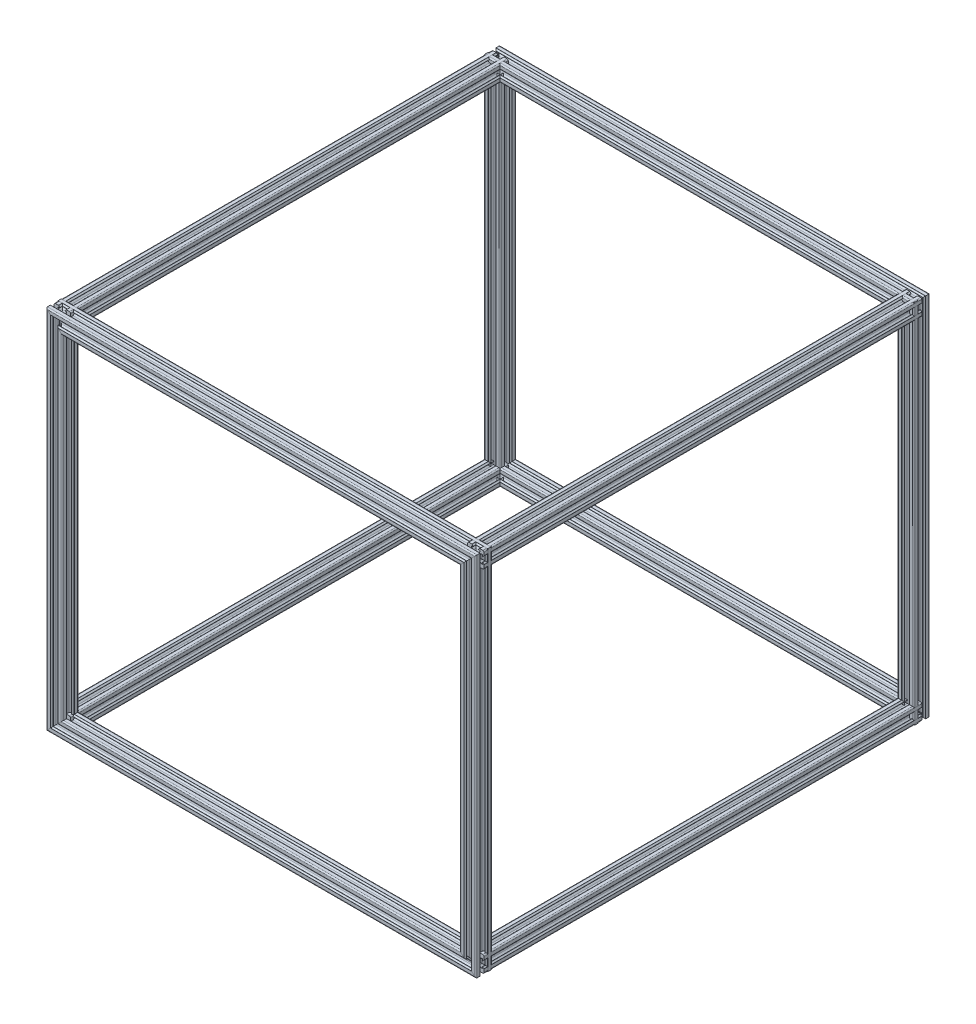
SolidWorks part; units mm, degrees
material "6061 Alloy"
ref_plane "Front Plane" through (0, 0, 0) normal (0, 0, 1) x (1, 0, 0)
ref_plane "Top Plane" through (0, 0, 0) normal (0, 1, 0) x (1, 0, 0)
ref_plane "Right Plane" through (0, 0, 0) normal (1, 0, 0) x (0, 0, -1)
sketch "Sketch1" plane through (0, 0, 0) normal (0, 0, 1) x (1, 0, 0)
  line L1 (-255, 215.9) -> (255, 215.9)
  line L2 (-255, 215.9) -> (-255, -215.9)
  line L3 (-255, -215.9) -> (255, -215.9)
  line L4 (255, 215.9) -> (255, -215.9)
  line L5 (-255, 215.9) -> (255, -215.9) construction
  line L6 (-255, -215.9) -> (255, 215.9) construction
  point P0 (0, 0)
  dimension "D1" = 510
  dimension "D2" = 431.8
ref_plane "Plane1" through (0, 0, 540) normal (0, 0, 1) x (1, 0, 0)
sketch3d "3DSketch2"
  line L0 (255, 215.9, 0) -> (255, -215.9, 0) construction
  line L1 (255, 215.9, 0) -> (255, -215.9, 0)
  line L2 (-255, 215.9, 0) -> (-255, -215.9, 0) construction
  line L3 (-255, 215.9, 0) -> (-255, -215.9, 0)
  line L8 (255, 215.9, 0) -> (-255, 215.9, 0)
  line L9 (255, -215.9, 0) -> (255, 215.9, 0)
  line L10 (-255, -215.9, 0) -> (255, -215.9, 0)
  line L11 (-255, 215.9, 0) -> (-255, -215.9, 0)
  line L12 (255, 215.9, 0) -> (-255, 215.9, 0)
  line L13 (255, -215.9, 0) -> (255, 215.9, 0)
  line L14 (-255, -215.9, 0) -> (255, -215.9, 0)
  line L15 (-255, 215.9, 0) -> (-255, -215.9, 0)
  dimension "D1" = 0
sketch "Sketch2" plane through (0, 0, 540) normal (0, 0, 1) x (1, 0, 0)
  line L4 (255, 215.9) -> (-255, 215.9)
  line L5 (255, -215.9) -> (255, 215.9)
  line L6 (-255, -215.9) -> (255, -215.9)
  line L7 (-255, 215.9) -> (-255, -215.9)
  line L8 (255, 215.9) -> (-255, 215.9)
  line L9 (255, -215.9) -> (255, 215.9)
  line L10 (-255, -215.9) -> (255, -215.9)
  line L11 (-255, 215.9) -> (-255, -215.9)
  dimension "D1" = 0
sketch3d "3DSketch3"
  line L0 (255, 215.9, 0) -> (255, 215.9, 540)
  line L1 (-255, 215.9, 0) -> (-255, 215.9, 540)
  line L2 (-255, -215.9, 0) -> (-255, -215.9, 540)
  line L3 (255, -215.9, 0) -> (255, -215.9, 540)
other "Profile_20х20 20X20(1)" corner treatment miter
ref_plane "Plane2" through (-255, 215.9, 540) normal (0, -1, 0) x (1, 0, 0)
sketch "Сечение" plane through (-255, 215.9, 540) normal (0, -1, 0) x (1, 0, 0)
  line L0 (-4, 1.8988) -> (-4, 0.3377)
  line L1 (-3.9452, 0.1815) -> (-3.8, 0)
  line L2 (-3.8, 0) -> (-3.9452, -0.1815)
  line L3 (-4, -0.3377) -> (-4, -1.8988)
  line L4 (-4.5858, -3.313) -> (-6.2799, -5.0071)
  line L5 (-6.987, -5.3) -> (-7.8, -5.3)
  line L6 (-8, -5.1) -> (-8, -3.33)
  line L7 (-8.4268, -3.1532) -> (-9.9268, -4.6532)
  line L8 (-10, -4.83) -> (-10, -8.5)
  line L9 (-8.5, -10) -> (-4.83, -10)
  line L10 (-4.6532, -9.9268) -> (-3.1532, -8.4268)
  line L11 (-3.33, -8) -> (-5.1, -8)
  line L12 (-5.3, -7.8) -> (-5.3, -6.987)
  line L13 (-5.0071, -6.2799) -> (-3.313, -4.5858)
  line L14 (-1.8988, -4) -> (-0.3377, -4)
  line L15 (-0.1815, -3.9452) -> (0, -3.8)
  line L16 (0, -3.8) -> (0.1815, -3.9452)
  line L17 (0.3377, -4) -> (1.8988, -4)
  line L18 (3.313, -4.5858) -> (5.0071, -6.2799)
  line L19 (5.3, -6.987) -> (5.3, -7.8)
  line L20 (5.1, -8) -> (3.33, -8)
  line L21 (3.1532, -8.4268) -> (4.6532, -9.9268)
  line L22 (4.83, -10) -> (8.5, -10)
  line L23 (10, -8.5) -> (10, -4.83)
  line L24 (9.9268, -4.6532) -> (8.4268, -3.1532)
  line L25 (8, -3.33) -> (8, -5.1)
  line L26 (7.8, -5.3) -> (6.987, -5.3)
  line L27 (6.2799, -5.0071) -> (4.5858, -3.313)
  line L28 (4, -1.8988) -> (4, -0.3377)
  line L29 (3.9452, -0.1815) -> (3.8, 0)
  line L30 (3.8, 0) -> (3.9452, 0.1815)
  line L31 (4, 0.3377) -> (4, 1.8988)
  line L32 (4.5858, 3.313) -> (6.2799, 5.0071)
  line L33 (6.987, 5.3) -> (7.8, 5.3)
  line L34 (8, 5.1) -> (8, 3.33)
  line L35 (8.4268, 3.1532) -> (9.9268, 4.6532)
  line L36 (10, 4.83) -> (10, 8.5)
  line L37 (8.5, 10) -> (4.83, 10)
  line L38 (4.6532, 9.9268) -> (3.1532, 8.4268)
  line L39 (3.33, 8) -> (5.1, 8)
  line L40 (5.3, 7.8) -> (5.3, 6.987)
  line L41 (5.0071, 6.2799) -> (3.313, 4.5858)
  line L42 (1.8988, 4) -> (0.3377, 4)
  line L43 (0.1815, 3.9452) -> (0, 3.8)
  line L44 (0, 3.8) -> (-0.1815, 3.9452)
  line L45 (-0.3377, 4) -> (-1.8988, 4)
  line L46 (-3.313, 4.5858) -> (-5.0071, 6.2799)
  line L47 (-5.3, 6.987) -> (-5.3, 7.8)
  line L48 (-5.1, 8) -> (-3.33, 8)
  line L49 (-3.1532, 8.4268) -> (-4.6532, 9.9268)
  line L50 (-4.83, 10) -> (-8.5, 10)
  line L51 (-10, 8.5) -> (-10, 4.83)
  line L52 (-9.9268, 4.6532) -> (-8.4268, 3.1532)
  line L53 (-8, 3.33) -> (-8, 5.1)
  line L54 (-7.8, 5.3) -> (-6.987, 5.3)
  line L55 (-6.2799, 5.0071) -> (-4.5858, 3.313)
  circle A0 centre (0, 0) radius 2.5
  arc A1 (-4, 0.3377) -> (-3.9452, 0.1815) centre (-3.75, 0.3377) ccw
  arc A2 (-3.9452, -0.1815) -> (-4, -0.3377) centre (-3.75, -0.3377) ccw
  arc A3 (-4, -1.8988) -> (-4.5858, -3.313) centre (-6, -1.8988) cw
  arc A4 (-6.2799, -5.0071) -> (-6.987, -5.3) centre (-6.987, -4.3) cw
  arc A5 (-7.8, -5.3) -> (-8, -5.1) centre (-7.8, -5.1) cw
  arc A6 (-8, -3.33) -> (-8.4268, -3.1532) centre (-8.25, -3.33) ccw
  arc A7 (-9.9268, -4.6532) -> (-10, -4.83) centre (-9.75, -4.83) ccw
  arc A8 (-10, -8.5) -> (-8.5, -10) centre (-8.5, -8.5) ccw
  arc A9 (-4.83, -10) -> (-4.6532, -9.9268) centre (-4.83, -9.75) ccw
  arc A10 (-3.1532, -8.4268) -> (-3.33, -8) centre (-3.33, -8.25) ccw
  arc A11 (-5.1, -8) -> (-5.3, -7.8) centre (-5.1, -7.8) cw
  arc A12 (-5.3, -6.987) -> (-5.0071, -6.2799) centre (-4.3, -6.987) cw
  arc A13 (-3.313, -4.5858) -> (-1.8988, -4) centre (-1.8988, -6) cw
  arc A14 (-0.3377, -4) -> (-0.1815, -3.9452) centre (-0.3377, -3.75) ccw
  arc A15 (0.1815, -3.9452) -> (0.3377, -4) centre (0.3377, -3.75) ccw
  arc A16 (1.8988, -4) -> (3.313, -4.5858) centre (1.8988, -6) cw
  arc A17 (5.0071, -6.2799) -> (5.3, -6.987) centre (4.3, -6.987) cw
  arc A18 (5.3, -7.8) -> (5.1, -8) centre (5.1, -7.8) cw
  arc A19 (3.33, -8) -> (3.1532, -8.4268) centre (3.33, -8.25) ccw
  arc A20 (4.6532, -9.9268) -> (4.83, -10) centre (4.83, -9.75) ccw
  arc A21 (8.5, -10) -> (10, -8.5) centre (8.5, -8.5) ccw
  arc A22 (10, -4.83) -> (9.9268, -4.6532) centre (9.75, -4.83) ccw
  arc A23 (8.4268, -3.1532) -> (8, -3.33) centre (8.25, -3.33) ccw
  arc A24 (8, -5.1) -> (7.8, -5.3) centre (7.8, -5.1) cw
  arc A25 (6.987, -5.3) -> (6.2799, -5.0071) centre (6.987, -4.3) cw
  arc A26 (4.5858, -3.313) -> (4, -1.8988) centre (6, -1.8988) cw
  arc A27 (4, -0.3377) -> (3.9452, -0.1815) centre (3.75, -0.3377) ccw
  arc A28 (3.9452, 0.1815) -> (4, 0.3377) centre (3.75, 0.3377) ccw
  arc A29 (4, 1.8988) -> (4.5858, 3.313) centre (6, 1.8988) cw
  arc A30 (6.2799, 5.0071) -> (6.987, 5.3) centre (6.987, 4.3) cw
  arc A31 (7.8, 5.3) -> (8, 5.1) centre (7.8, 5.1) cw
  arc A32 (8, 3.33) -> (8.4268, 3.1532) centre (8.25, 3.33) ccw
  arc A33 (9.9268, 4.6532) -> (10, 4.83) centre (9.75, 4.83) ccw
  arc A34 (10, 8.5) -> (8.5, 10) centre (8.5, 8.5) ccw
  arc A35 (4.83, 10) -> (4.6532, 9.9268) centre (4.83, 9.75) ccw
  arc A36 (3.1532, 8.4268) -> (3.33, 8) centre (3.33, 8.25) ccw
  arc A37 (5.1, 8) -> (5.3, 7.8) centre (5.1, 7.8) cw
  arc A38 (5.3, 6.987) -> (5.0071, 6.2799) centre (4.3, 6.987) cw
  arc A39 (3.313, 4.5858) -> (1.8988, 4) centre (1.8988, 6) cw
  arc A40 (0.3377, 4) -> (0.1815, 3.9452) centre (0.3377, 3.75) ccw
  arc A41 (-0.1815, 3.9452) -> (-0.3377, 4) centre (-0.3377, 3.75) ccw
  arc A42 (-1.8988, 4) -> (-3.313, 4.5858) centre (-1.8988, 6) cw
  arc A43 (-5.0071, 6.2799) -> (-5.3, 6.987) centre (-4.3, 6.987) cw
  arc A44 (-5.3, 7.8) -> (-5.1, 8) centre (-5.1, 7.8) cw
  arc A45 (-3.33, 8) -> (-3.1532, 8.4268) centre (-3.33, 8.25) ccw
  arc A46 (-4.6532, 9.9268) -> (-4.83, 10) centre (-4.83, 9.75) ccw
  arc A47 (-8.5, 10) -> (-10, 8.5) centre (-8.5, 8.5) ccw
  arc A48 (-10, 4.83) -> (-9.9268, 4.6532) centre (-9.75, 4.83) ccw
  arc A49 (-8.4268, 3.1532) -> (-8, 3.33) centre (-8.25, 3.33) ccw
  arc A50 (-8, 5.1) -> (-7.8, 5.3) centre (-7.8, 5.1) cw
  arc A51 (-6.987, 5.3) -> (-6.2799, 5.0071) centre (-6.987, 4.3) cw
  arc A52 (-4.5858, 3.313) -> (-4, 1.8988) centre (-6, 1.8988) cw
  point P162 (0, 0)
other "Profile_20х20 20X20(2)" corner treatment miter
ref_plane "Plane3" through (-255, 215.9, 0) normal (0, 0, 1) x (1, 0, 0)
sketch "Сечение1" plane through (-255, 215.9, 0) normal (0, 0, 1) x (1, 0, 0)
  line L0 (-4, 1.8988) -> (-4, 0.3377)
  line L1 (-3.9452, 0.1815) -> (-3.8, 0)
  line L2 (-3.8, 0) -> (-3.9452, -0.1815)
  line L3 (-4, -0.3377) -> (-4, -1.8988)
  line L4 (-4.5858, -3.313) -> (-6.2799, -5.0071)
  line L5 (-6.987, -5.3) -> (-7.8, -5.3)
  line L6 (-8, -5.1) -> (-8, -3.33)
  line L7 (-8.4268, -3.1532) -> (-9.9268, -4.6532)
  line L8 (-10, -4.83) -> (-10, -8.5)
  line L9 (-8.5, -10) -> (-4.83, -10)
  line L10 (-4.6532, -9.9268) -> (-3.1532, -8.4268)
  line L11 (-3.33, -8) -> (-5.1, -8)
  line L12 (-5.3, -7.8) -> (-5.3, -6.987)
  line L13 (-5.0071, -6.2799) -> (-3.313, -4.5858)
  line L14 (-1.8988, -4) -> (-0.3377, -4)
  line L15 (-0.1815, -3.9452) -> (0, -3.8)
  line L16 (0, -3.8) -> (0.1815, -3.9452)
  line L17 (0.3377, -4) -> (1.8988, -4)
  line L18 (3.313, -4.5858) -> (5.0071, -6.2799)
  line L19 (5.3, -6.987) -> (5.3, -7.8)
  line L20 (5.1, -8) -> (3.33, -8)
  line L21 (3.1532, -8.4268) -> (4.6532, -9.9268)
  line L22 (4.83, -10) -> (8.5, -10)
  line L23 (10, -8.5) -> (10, -4.83)
  line L24 (9.9268, -4.6532) -> (8.4268, -3.1532)
  line L25 (8, -3.33) -> (8, -5.1)
  line L26 (7.8, -5.3) -> (6.987, -5.3)
  line L27 (6.2799, -5.0071) -> (4.5858, -3.313)
  line L28 (4, -1.8988) -> (4, -0.3377)
  line L29 (3.9452, -0.1815) -> (3.8, 0)
  line L30 (3.8, 0) -> (3.9452, 0.1815)
  line L31 (4, 0.3377) -> (4, 1.8988)
  line L32 (4.5858, 3.313) -> (6.2799, 5.0071)
  line L33 (6.987, 5.3) -> (7.8, 5.3)
  line L34 (8, 5.1) -> (8, 3.33)
  line L35 (8.4268, 3.1532) -> (9.9268, 4.6532)
  line L36 (10, 4.83) -> (10, 8.5)
  line L37 (8.5, 10) -> (4.83, 10)
  line L38 (4.6532, 9.9268) -> (3.1532, 8.4268)
  line L39 (3.33, 8) -> (5.1, 8)
  line L40 (5.3, 7.8) -> (5.3, 6.987)
  line L41 (5.0071, 6.2799) -> (3.313, 4.5858)
  line L42 (1.8988, 4) -> (0.3377, 4)
  line L43 (0.1815, 3.9452) -> (0, 3.8)
  line L44 (0, 3.8) -> (-0.1815, 3.9452)
  line L45 (-0.3377, 4) -> (-1.8988, 4)
  line L46 (-3.313, 4.5858) -> (-5.0071, 6.2799)
  line L47 (-5.3, 6.987) -> (-5.3, 7.8)
  line L48 (-5.1, 8) -> (-3.33, 8)
  line L49 (-3.1532, 8.4268) -> (-4.6532, 9.9268)
  line L50 (-4.83, 10) -> (-8.5, 10)
  line L51 (-10, 8.5) -> (-10, 4.83)
  line L52 (-9.9268, 4.6532) -> (-8.4268, 3.1532)
  line L53 (-8, 3.33) -> (-8, 5.1)
  line L54 (-7.8, 5.3) -> (-6.987, 5.3)
  line L55 (-6.2799, 5.0071) -> (-4.5858, 3.313)
  circle A0 centre (0, 0) radius 2.5
  arc A1 (-4, 0.3377) -> (-3.9452, 0.1815) centre (-3.75, 0.3377) ccw
  arc A2 (-3.9452, -0.1815) -> (-4, -0.3377) centre (-3.75, -0.3377) ccw
  arc A3 (-4, -1.8988) -> (-4.5858, -3.313) centre (-6, -1.8988) cw
  arc A4 (-6.2799, -5.0071) -> (-6.987, -5.3) centre (-6.987, -4.3) cw
  arc A5 (-7.8, -5.3) -> (-8, -5.1) centre (-7.8, -5.1) cw
  arc A6 (-8, -3.33) -> (-8.4268, -3.1532) centre (-8.25, -3.33) ccw
  arc A7 (-9.9268, -4.6532) -> (-10, -4.83) centre (-9.75, -4.83) ccw
  arc A8 (-10, -8.5) -> (-8.5, -10) centre (-8.5, -8.5) ccw
  arc A9 (-4.83, -10) -> (-4.6532, -9.9268) centre (-4.83, -9.75) ccw
  arc A10 (-3.1532, -8.4268) -> (-3.33, -8) centre (-3.33, -8.25) ccw
  arc A11 (-5.1, -8) -> (-5.3, -7.8) centre (-5.1, -7.8) cw
  arc A12 (-5.3, -6.987) -> (-5.0071, -6.2799) centre (-4.3, -6.987) cw
  arc A13 (-3.313, -4.5858) -> (-1.8988, -4) centre (-1.8988, -6) cw
  arc A14 (-0.3377, -4) -> (-0.1815, -3.9452) centre (-0.3377, -3.75) ccw
  arc A15 (0.1815, -3.9452) -> (0.3377, -4) centre (0.3377, -3.75) ccw
  arc A16 (1.8988, -4) -> (3.313, -4.5858) centre (1.8988, -6) cw
  arc A17 (5.0071, -6.2799) -> (5.3, -6.987) centre (4.3, -6.987) cw
  arc A18 (5.3, -7.8) -> (5.1, -8) centre (5.1, -7.8) cw
  arc A19 (3.33, -8) -> (3.1532, -8.4268) centre (3.33, -8.25) ccw
  arc A20 (4.6532, -9.9268) -> (4.83, -10) centre (4.83, -9.75) ccw
  arc A21 (8.5, -10) -> (10, -8.5) centre (8.5, -8.5) ccw
  arc A22 (10, -4.83) -> (9.9268, -4.6532) centre (9.75, -4.83) ccw
  arc A23 (8.4268, -3.1532) -> (8, -3.33) centre (8.25, -3.33) ccw
  arc A24 (8, -5.1) -> (7.8, -5.3) centre (7.8, -5.1) cw
  arc A25 (6.987, -5.3) -> (6.2799, -5.0071) centre (6.987, -4.3) cw
  arc A26 (4.5858, -3.313) -> (4, -1.8988) centre (6, -1.8988) cw
  arc A27 (4, -0.3377) -> (3.9452, -0.1815) centre (3.75, -0.3377) ccw
  arc A28 (3.9452, 0.1815) -> (4, 0.3377) centre (3.75, 0.3377) ccw
  arc A29 (4, 1.8988) -> (4.5858, 3.313) centre (6, 1.8988) cw
  arc A30 (6.2799, 5.0071) -> (6.987, 5.3) centre (6.987, 4.3) cw
  arc A31 (7.8, 5.3) -> (8, 5.1) centre (7.8, 5.1) cw
  arc A32 (8, 3.33) -> (8.4268, 3.1532) centre (8.25, 3.33) ccw
  arc A33 (9.9268, 4.6532) -> (10, 4.83) centre (9.75, 4.83) ccw
  arc A34 (10, 8.5) -> (8.5, 10) centre (8.5, 8.5) ccw
  arc A35 (4.83, 10) -> (4.6532, 9.9268) centre (4.83, 9.75) ccw
  arc A36 (3.1532, 8.4268) -> (3.33, 8) centre (3.33, 8.25) ccw
  arc A37 (5.1, 8) -> (5.3, 7.8) centre (5.1, 7.8) cw
  arc A38 (5.3, 6.987) -> (5.0071, 6.2799) centre (4.3, 6.987) cw
  arc A39 (3.313, 4.5858) -> (1.8988, 4) centre (1.8988, 6) cw
  arc A40 (0.3377, 4) -> (0.1815, 3.9452) centre (0.3377, 3.75) ccw
  arc A41 (-0.1815, 3.9452) -> (-0.3377, 4) centre (-0.3377, 3.75) ccw
  arc A42 (-1.8988, 4) -> (-3.313, 4.5858) centre (-1.8988, 6) cw
  arc A43 (-5.0071, 6.2799) -> (-5.3, 6.987) centre (-4.3, 6.987) cw
  arc A44 (-5.3, 7.8) -> (-5.1, 8) centre (-5.1, 7.8) cw
  arc A45 (-3.33, 8) -> (-3.1532, 8.4268) centre (-3.33, 8.25) ccw
  arc A46 (-4.6532, 9.9268) -> (-4.83, 10) centre (-4.83, 9.75) ccw
  arc A47 (-8.5, 10) -> (-10, 8.5) centre (-8.5, 8.5) ccw
  arc A48 (-10, 4.83) -> (-9.9268, 4.6532) centre (-9.75, 4.83) ccw
  arc A49 (-8.4268, 3.1532) -> (-8, 3.33) centre (-8.25, 3.33) ccw
  arc A50 (-8, 5.1) -> (-7.8, 5.3) centre (-7.8, 5.1) cw
  arc A51 (-6.987, 5.3) -> (-6.2799, 5.0071) centre (-6.987, 4.3) cw
  arc A52 (-4.5858, 3.313) -> (-4, 1.8988) centre (-6, 1.8988) cw
  point P162 (0, 0)
